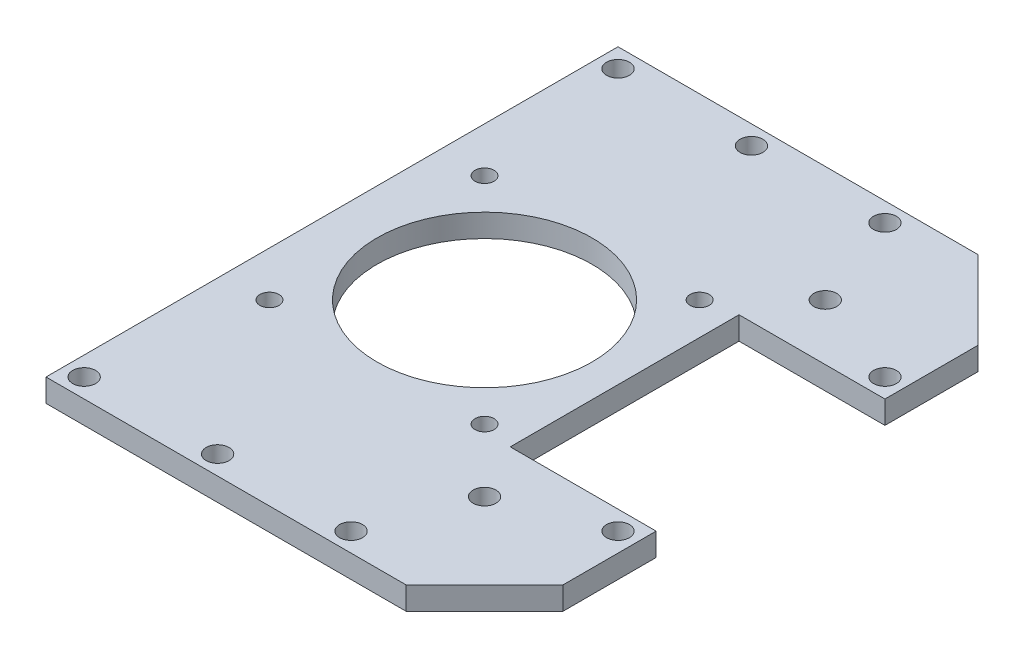
SolidWorks part; units mm, degrees
ref_plane "前视基准面" through (0, 0, 0) normal (0, 0, 1) x (1, 0, 0)
ref_plane "上视基准面" through (0, 0, 0) normal (0, 1, 0) x (1, 0, 0)
ref_plane "右视基准面" through (0, 0, 0) normal (1, 0, 0) x (0, 0, -1)
other "Configuration Table"
sketch "草图1" plane through (0, 0, 0) normal (0, 1, 0) x (1, 0, 0)
  line L4 (37.5, 27.2031) -> (37.5, 15)
  line L5 (-37.5, 37.5) -> (37.5, -37.5) construction
  line L6 (-37.5, -37.5) -> (37.5, 37.5) construction
  line L11 (-14.1, 14.1) -> (14.1, 14.1) construction
  line L12 (-14.1, 14.1) -> (-14.1, -14.1) construction
  line L13 (-14.1, -14.1) -> (14.1, -14.1) construction
  line L14 (14.1, 14.1) -> (14.1, -14.1) construction
  line L15 (-14.1, 14.1) -> (14.1, -14.1) construction
  line L16 (-14.1, -14.1) -> (14.1, 14.1) construction
  line L17 (37.5, 27.2031) -> (27.2031, 37.5)
  line L18 (-37.5, 0) -> (37.5, 0) construction
  line L19 (27.2031, 37.5) -> (-20, 37.5)
  line L20 (37.5, -27.2031) -> (27.2031, -37.5)
  line L21 (27.2031, -37.5) -> (-20, -37.5)
  line L22 (-20, 37.5) -> (-20, -37.5)
  line L23 (27.2031, 37.5) -> (37.5, 27.2031) construction
  line L24 (37.5, 27.2031) -> (37.5, 15) construction
  line L25 (37.5, 15) -> (18.3705, 15)
  line L26 (18.3705, 15) -> (18.3705, -15)
  line L27 (18.3705, -15) -> (37.5, -15)
  line L29 (37.5, -15) -> (37.5, -27.2031)
  circle A3 centre (17.5, 35) radius 1.5
  circle A4 centre (22.3377, 22.3377) radius 1.5
  circle A5 centre (35, 17.5) radius 1.5
  circle A9 centre (17.5, -35) radius 1.5
  circle A10 centre (22.3377, -22.3377) radius 1.5
  circle A11 centre (35, -17.5) radius 1.5
  circle A12 centre (-14.1, 14.1) radius 1.25
  circle A13 centre (14.1, -14.1) radius 1.25
  circle A14 centre (0, 35) radius 1.5
  circle A15 centre (-17.5, 35) radius 1.5
  circle A16 centre (0, -35) radius 1.5
  circle A17 centre (-17.5, -35) radius 1.5
  circle A18 centre (14.1, 14.1) radius 1.25
  circle A19 centre (-14.1, -14.1) radius 1.25
  circle A20 centre (0, 0) radius 14.1
  arc A21 (18.5366, 13.75) -> (13.75, 18.5366) centre (13.75, 13.75) ccw construction
  point P0 (0, 0)
  point P58 (0, 0)
  dimension "D5" = 2.5
  dimension "D6" = 2.5
  dimension "D9" = 2.5
  dimension "D10" = 2.5
  dimension "D1" = 75
  dimension "D2" = 75
  dimension "D3" = 28.2
  dimension "D4" = 28.2
  dimension "D8" = 2.5
  dimension "D7" = 3
extrude "凸台-拉伸1" add sketch "草图1" along normal blind 3
